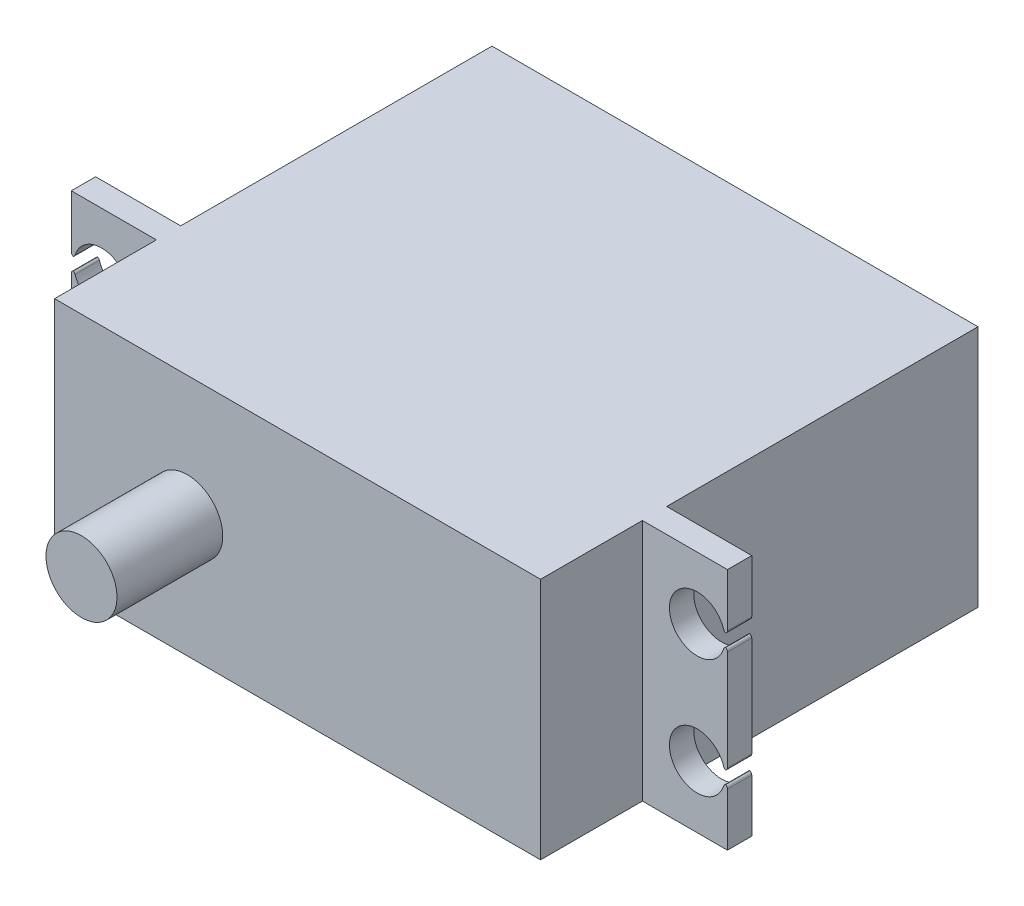
SolidWorks part; units mm, degrees
ref_plane "Front Plane" through (0, 0, 0) normal (0, 0, 1) x (1, 0, 0)
ref_plane "Top Plane" through (0, 0, 0) normal (0, 1, 0) x (1, 0, 0)
ref_plane "Right Plane" through (0, 0, 0) normal (1, 0, 0) x (0, 0, -1)
sketch "Sketch1" plane through (0, 0, 0) normal (0, 1, 0) x (1, 0, 0)
  line L1 (-20, -18) -> (20, -18)
  line L2 (-20, -18) -> (-20, 18)
  line L3 (-20, 18) -> (20, 18)
  line L4 (20, -18) -> (20, 18)
  line L5 (-20, -18) -> (20, 18) construction
  line L6 (-20, 18) -> (20, -18) construction
  point P0 (0, 0)
  dimension "D1" = 40
  dimension "D2" = 36
extrude "Boss-Extrude1" add sketch "Sketch1" along normal mid plane 20
sketch "Sketch2" plane through (0, 0, 0) normal (0, 0, 1) x (1, 0, 0)
  line L0 (-20, -10) -> (20, -10) construction
  line L1 (-20, 10) -> (-27, 10)
  line L2 (-20, 10) -> (-20, -10)
  line L3 (-20, -10) -> (-27, -10)
  line L4 (-27, 10) -> (-27, -10)
  line L5 (20, 10) -> (27, 10)
  line L6 (20, 10) -> (20, -10)
  line L7 (20, -10) -> (27, -10)
  line L8 (27, 10) -> (27, -10)
  dimension "D1" = 54
extrude "Boss-Extrude2" add sketch "Sketch2" along normal blind 2 from offset 7.62
sketch "Sketch3" plane through (0, 0, 0) normal (0, 0, 1) x (1, 0, 0)
  line L0 (21.197, 0) -> (-21.197, 0) construction
  line L1 (-2.54, 0) -> (2.54, 0)
  line L2 (-2.54, 0) -> (-2.54, 25.4)
  line L3 (-2.54, 25.4) -> (2.54, 25.4)
  line L4 (2.54, 0) -> (2.54, 25.4)
  point P6 (0, 25.4)
  dimension "D1" = 5.08
  dimension "D2" = 25.4
sketch "Sketch4" plane through (0, 0, 0) normal (0, 0, 1) x (1, 0, 0)
  line L0 (-24.511, 4.885) -> (24.511, 4.885) construction
  line L1 (-24.511, -4.885) -> (24.511, -4.885) construction
  line L2 (0, 4.885) -> (0, -4.885) construction
  line L3 (-27, 10) -> (-27, -10) construction
  line L4 (-27, 5.393) -> (-26.7398, 5.393)
  line L5 (-27, 5.393) -> (-27, 4.377)
  line L6 (-27, 4.377) -> (-26.7398, 4.377)
  line L8 (27, 4.377) -> (26.7398, 4.377)
  line L9 (27, 5.393) -> (27, 4.377)
  line L10 (27, 5.393) -> (26.7398, 5.393)
  line L11 (24.5872, 0) -> (-24.5872, 0) construction
  line L12 (27, -5.393) -> (26.7398, -5.393)
  line L13 (27, -5.393) -> (27, -4.377)
  line L14 (27, -4.377) -> (26.7398, -4.377)
  line L15 (-27, -4.377) -> (-26.7398, -4.377)
  line L16 (-27, -5.393) -> (-27, -4.377)
  line L17 (-27, -5.393) -> (-26.7398, -5.393)
  arc A0 (-26.7398, 4.377) -> (-26.7398, 5.393) centre (-24.511, 4.885) ccw
  arc A1 (26.7398, 4.377) -> (26.7398, 5.393) centre (24.511, 4.885) cw
  arc A2 (26.7398, -4.377) -> (26.7398, -5.393) centre (24.511, -4.885) ccw
  arc A3 (-26.7398, -4.377) -> (-26.7398, -5.393) centre (-24.511, -4.885) cw
  point P3 (0, 4.885)
  point P9 (0, 0)
  point P10 (-26.4028, 5.6539)
  point P16 (-26.2166, 6.0504)
  dimension "D3" = 4.572
  dimension "D1" = 49.022
  dimension "D2" = 9.77
  dimension "D4" = 1.016
extrude "Cut-Extrude1" cut sketch "Sketch4" against normal through all both and the other way through all
fillet "Fillet1" radius 0.254 16 edges at (26.7398, -5.393, 8.62) (27, -4.377, 8.62) (26.7398, 4.377, 8.62) (26.7398, 5.393, 8.62) (-27, -5.393, 8.62) (-27, -4.377, 8.62) (-27, 4.377, 8.62) (-27, 5.393, 8.62) (27, 5.393, 8.62) (27, 4.377, 8.62) (26.7398, -4.377, 8.62) (27, -5.393, 8.62) (-26.7398, -5.393, 8.62) (-26.7398, -4.377, 8.62) (-26.7398, 4.377, 8.62) (-26.7398, 5.393, 8.62)
sketch "Sketch5" plane through (0, 0, 0) normal (0, 0, 1) x (1, 0, 0)
  line L0 (-20, 0) -> (-9.078, 0) construction
  line L1 (-20, -10) -> (-20, 10) construction
  circle A0 centre (-9.078, 0) radius 2.921
  dimension "D2" = 5.842
  dimension "D1" = 10.922
extrude "Boss-Extrude4" add sketch "Sketch5" along normal offset from surface (8.704 mm away) 44.704 from surface up to face at (0, 0, -18) starting at face at (0, 0, 18)
